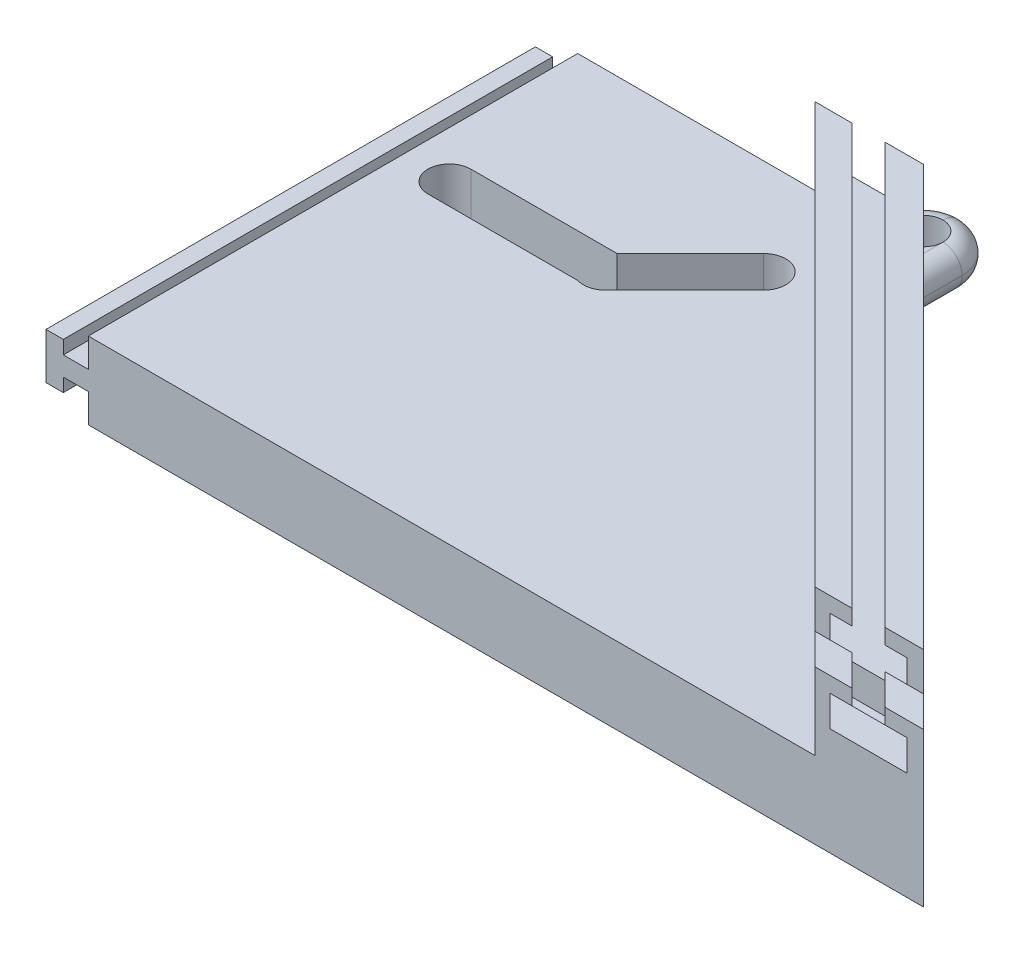
SolidWorks part; units mm, degrees
ref_plane "Front Plane" through (0, 0, 0) normal (0, 0, 1) x (1, 0, 0)
ref_plane "Top Plane" through (0, 0, 0) normal (0, 1, 0) x (1, 0, 0)
ref_plane "Right Plane" through (0, 0, 0) normal (1, 0, 0) x (0, 0, -1)
sketch "Sketch1" plane through (0, 0, 0) normal (0, 1, 0) x (1, 0, 0)
  line L0 (-11.6729, -34.564) -> (96.9667, -34.564)
  line L1 (96.9667, -34.564) -> (33.3271, 29.0756)
  line L2 (33.3271, 29.0756) -> (-11.6729, 29.0756)
  line L3 (-11.6729, 29.0756) -> (-11.6729, -34.564)
  dimension "D1" = 45
  dimension "D2" = 45
  dimension "D3" = 90
extrude "Boss-Extrude1" add sketch "Sketch1" along normal blind 10
sketch "Sketch2" plane through (0, 0, 34.564) normal (0, 0, 1) x (1, 0, 0)
  line L0 (-11.6729, 3.75) -> (-14.9229, 3.75)
  line L1 (-11.6729, 10) -> (-11.6729, 0) construction
  line L2 (-14.9229, 3.75) -> (-14.9229, 2)
  line L3 (-14.9229, 2) -> (-17.1729, 2)
  line L4 (-17.1729, 2) -> (-17.1729, 8)
  line L5 (-17.1729, 8) -> (-14.9229, 8)
  line L6 (-14.9229, 8) -> (-14.9229, 6.25)
  line L7 (-14.9229, 6.25) -> (-11.6729, 6.25)
  line L8 (-11.6729, 6.25) -> (-11.6729, 3.75)
  line L9 (-11.6729, 0) -> (96.9667, 0) construction
  line L10 (-11.6729, 10) -> (96.9667, 10) construction
  dimension "D1" = 3.75
  dimension "D2" = 3.75
  dimension "D3" = 1.75
  dimension "D4" = 1.75
  dimension "D5" = 2.25
  dimension "D6" = 3.25
  dimension "D7" = 3.25
extrude "Boss-Extrude3" add sketch "Sketch2" against normal blind 65
sketch "Sketch3" plane through (0, 8, 0) normal (0, 1, 0) x (1, 0, 0)
  line L0 (33.3271, 29.0756) -> (-11.6729, 29.0756) construction
  line L1 (-17.1729, 30.436) -> (-10.6059, 30.436)
  line L2 (-17.1729, 30.436) -> (-17.1729, 29.0756)
  line L3 (-17.1729, 29.0756) -> (-10.6059, 29.0756)
  line L4 (-10.6059, 30.436) -> (-10.6059, 29.0756)
  dimension "D1" = 0
extrude "Cut-Extrude2" cut sketch "Sketch3" against normal blind 65
sketch "Sketch4" plane through (0, 10, 0) normal (0, 1, 0) x (1, 0, 0)
  line L0 (91.6634, -34.564) -> (28.0238, 29.0756)
  line L1 (-11.6729, -34.564) -> (96.9667, -34.564) construction
  line L2 (33.3271, 29.0756) -> (-11.6729, 29.0756) construction
  line L3 (28.0238, 29.0756) -> (25.5206, 29.0756)
  line L4 (25.5206, 29.0756) -> (89.1602, -34.564)
  line L5 (89.1602, -34.564) -> (91.6634, -34.564)
  line L6 (96.9667, -34.564) -> (33.3271, 29.0756) construction
  dimension "D1" = 3.75
  dimension "D2" = 1.77
extrude "Boss-Extrude4" add sketch "Sketch4" along normal blind 3.25
sketch "Sketch6" plane through (0, 13.25, 0) normal (0, 1, 0) x (1, 0, 0)
  line L0 (90.4118, -34.564) -> (94.1368, -34.564)
  line L1 (89.1602, -34.564) -> (91.6634, -34.564) construction
  line L2 (94.1368, -34.564) -> (30.4972, 29.0756)
  line L3 (30.4972, 29.0756) -> (23.0472, 29.0756)
  line L4 (23.0472, 29.0756) -> (86.6868, -34.564)
  line L5 (86.6868, -34.564) -> (90.4118, -34.564)
  line L6 (28.0238, 29.0756) -> (25.5206, 29.0756) construction
  dimension "D1" = 7.45
  dimension "D2" = 3.725
  dimension "D3" = 3.725
  dimension "D4" = 0
  dimension "D5" = 45
extrude "Boss-Extrude5" add sketch "Sketch6" along normal blind 2.25
sketch "Sketch7" plane through (0, 0, -29.0756) normal (0, 0, -1) x (-1, 0, 0)
  line L0 (-33.3271, 10) -> (-33.3271, 0) construction
  line L1 (-33.3271, 2.5) -> (-23.3271, 2.5)
  line L2 (-33.3271, 2.5) -> (-33.3271, 7.5)
  line L3 (-33.3271, 7.5) -> (-23.3271, 7.5)
  line L4 (-23.3271, 2.5) -> (-23.3271, 7.5)
  line L5 (-33.3271, 0) -> (11.6729, 0) construction
  dimension "D1" = 10
  dimension "D2" = 5
  dimension "D3" = 2.5
extrude "Boss-Extrude6" add sketch "Sketch7" along normal blind 10
sketch "Sketch8" plane through (0, 7.5, 0) normal (0, 1, 0) x (1, 0, 0)
  line L0 (23.3271, 39.0756) -> (33.3271, 39.0756) construction
  line L1 (23.3271, 39.0756) -> (23.3271, 29.0756) construction
  circle A0 centre (28.3271, 34.0756) radius 2.5
  dimension "D1" = 5
  dimension "D2" = 5
  dimension "D3" = 5
extrude "Cut-Extrude3" cut sketch "Sketch8" against normal blind 10
fillet "Fillet1" radius 5 1 edges at (23.3271, 5, -39.0756) type face fillet first side face at (23.3271, 5, -34.0756) second side face at (28.3271, 5, -39.0756)
fillet "Fillet2" radius 5 1 edges at (33.3271, 5, -39.0756) type face fillet first side face at (30.8271, 5, -39.0756) second side face at (33.3271, 5, -34.0756)
fillet "Fillet4" radius 2.5 2 edges at (24.7916, 7.5, -37.6112) (23.3271, 7.5, -31.5756) type face fillet first side face at (25.3093, 5, -37.0934) first side face at (23.3271, 5, -31.5756) second side face at (28.3271, 7.5, -31.5756)
fillet "Fillet5" radius 2.5 2 edges at (24.7916, 2.5, -37.6112) (23.3271, 2.5, -31.5756) type face fillet first side face at (25.3093, 3.75, -37.0934) first side face at (23.3271, 3.75, -31.5756) second side face at (28.3271, 2.5, -31.5756)
sketch "Sketch9" plane through (0, 0, 34.564) normal (0, 0, 1) x (1, 0, 0)
  line L0 (-11.6729, 10) -> (89.1602, 10) construction
  line L1 (94.1368, 15.5) -> (-5.8632, 15.5)
  line L2 (94.1368, 15.5) -> (94.1368, 10)
  line L3 (94.1368, 10) -> (-5.8632, 10)
  line L4 (-5.8632, 15.5) -> (-5.8632, 10)
  dimension "D1" = 100
extrude "Cut-Extrude4" cut sketch "Sketch9" against normal blind 100
sketch "Sketch10" plane through (0, 10, 0) normal (0, 1, 0) x (1, 0, 0)
  line L0 (96.9667, -34.564) -> (89.8956, -41.6351)
  line L1 (89.8956, -41.6351) -> (7.417, 40.8436)
  line L2 (7.417, 40.8436) -> (14.4881, 47.9146)
  line L3 (14.4881, 47.9146) -> (96.9667, -34.564)
  dimension "D1" = 10
extrude "Boss-Extrude7" add sketch "Sketch10" along normal blind 10
sketch "Sketch11" plane through (65.7653, 0, 65.7653) normal (0.7071, 0, 0.7071) x (0.7071, 0, -0.7071)
  line L0 (40.5425, 20) -> (40.5425, 18)
  line L1 (34.1254, 20) -> (44.1254, 20) construction
  line L2 (40.5425, 18) -> (42.5925, 18)
  line L3 (42.5925, 18) -> (42.5925, 14)
  line L4 (42.5925, 14) -> (35.4925, 14)
  line L5 (35.4925, 14) -> (35.4925, 18)
  line L6 (35.4925, 18) -> (37.5425, 18)
  line L7 (37.5425, 18) -> (37.5425, 20)
  line L8 (37.5425, 20) -> (40.5425, 20)
  dimension "D1" = 2
  dimension "D2" = 7.1
  dimension "D3" = 3
  dimension "D4" = 2.05
  dimension "D5" = 4
extrude "Cut-Extrude5" cut sketch "Sketch11" against normal blind 150
sketch "Sketch12" plane through (0, 10, 0) normal (0, -1, 0) x (-1, 0, 0)
  line L0 (-33.3271, 29.0756) -> (-19.185, 29.0756) construction
  line L1 (-19.185, 29.0756) -> (-49.1058, 29.0756)
  line L2 (-19.185, 29.0756) -> (-19.185, 62.2793)
  line L3 (-19.185, 62.2793) -> (-49.1058, 62.2793)
  line L4 (-49.1058, 29.0756) -> (-49.1058, 62.2793)
extrude "Cut-Extrude6" cut sketch "Sketch12" against normal blind 150
sketch "Sketch14" plane through (0, 10, 0) normal (0, -1, 0) x (-1, 0, 0)
  line L0 (-19.185, 29.0756) -> (-19.185, 43.2178) construction
  line L1 (-19.185, 29.0756) -> (0, 29.0756)
  line L2 (-19.185, 29.0756) -> (-19.185, 57.2083)
  line L3 (-19.185, 57.2083) -> (0, 57.2083)
  line L4 (0, 29.0756) -> (0, 57.2083)
extrude "Cut-Extrude7" cut sketch "Sketch14" against normal blind 150
sketch "Sketch16" plane through (0, 10, 0) normal (0, -1, 0) x (-1, 0, 0)
  line L1 (-82.8246, -34.564) -> (-98.445, -34.564)
  line L2 (-82.8246, -34.564) -> (-82.8246, -45.3868)
  line L3 (-82.8246, -45.3868) -> (-98.445, -45.3868)
  line L4 (-98.445, -34.564) -> (-98.445, -45.3868)
extrude "Cut-Extrude8" cut sketch "Sketch16" against normal blind 150
sketch "Sketch17" plane through (0, 20, 0) normal (0, 1, 0) x (1, 0, 0)
  line L0 (92.9667, -30.564) -> (78.8246, -30.564)
  line L1 (96.9667, -34.564) -> (33.3271, 29.0756) construction
  line L2 (19.185, 29.0756) -> (82.8246, -34.564) construction
  line L3 (78.8246, -30.564) -> (73.8246, -25.564)
  line L4 (73.8246, -25.564) -> (87.9667, -25.564)
  line L5 (87.9667, -25.564) -> (92.9667, -30.564)
  line L6 (82.8246, -34.564) -> (87.6572, -34.564) construction
  dimension "D1" = 4
  dimension "D2" = 5
extrude "Cut-Extrude9" cut sketch "Sketch17" against normal blind 10
sketch "Sketch18" plane through (0, 10, 0) normal (0, 1, 0) x (1, 0, 0)
  line L0 (24.9905, 16.5621) -> (14.7427, 6.3142) construction
  line L1 (27.059, 14.4936) -> (16.8112, 4.2458)
  line L2 (22.9221, 18.6306) -> (12.6742, 8.3827)
  line L3 (14.7427, 6.3142) -> (-5.5955, 6.3142) construction
  line L4 (14.7427, 3.5173) -> (-5.5955, 3.5173)
  line L5 (14.7427, 9.1112) -> (-5.5955, 9.1112)
  arc A0 (27.059, 14.4936) -> (22.9221, 18.6306) centre (24.9905, 16.5621) ccw
  arc A1 (12.6742, 8.3827) -> (16.8112, 4.2458) centre (14.7427, 6.3142) ccw
  arc A2 (14.7427, 3.5173) -> (14.7427, 9.1112) centre (14.7427, 6.3142) ccw
  arc A3 (-5.5955, 9.1112) -> (-5.5955, 3.5173) centre (-5.5955, 6.3142) ccw
  point P2 (19.8666, 11.4382)
  point P7 (4.5736, 6.3142)
extrude "Cut-Extrude10" cut sketch "Sketch18" against normal blind 10 contours A2 L4 A1 L1 A0 L2 L5 | L4 A2 L5 L2 A1 | L4 A3 L5 A2 region at (21.4219, 10, -12.9652) region at (14.6577, 10, -6.3239)
